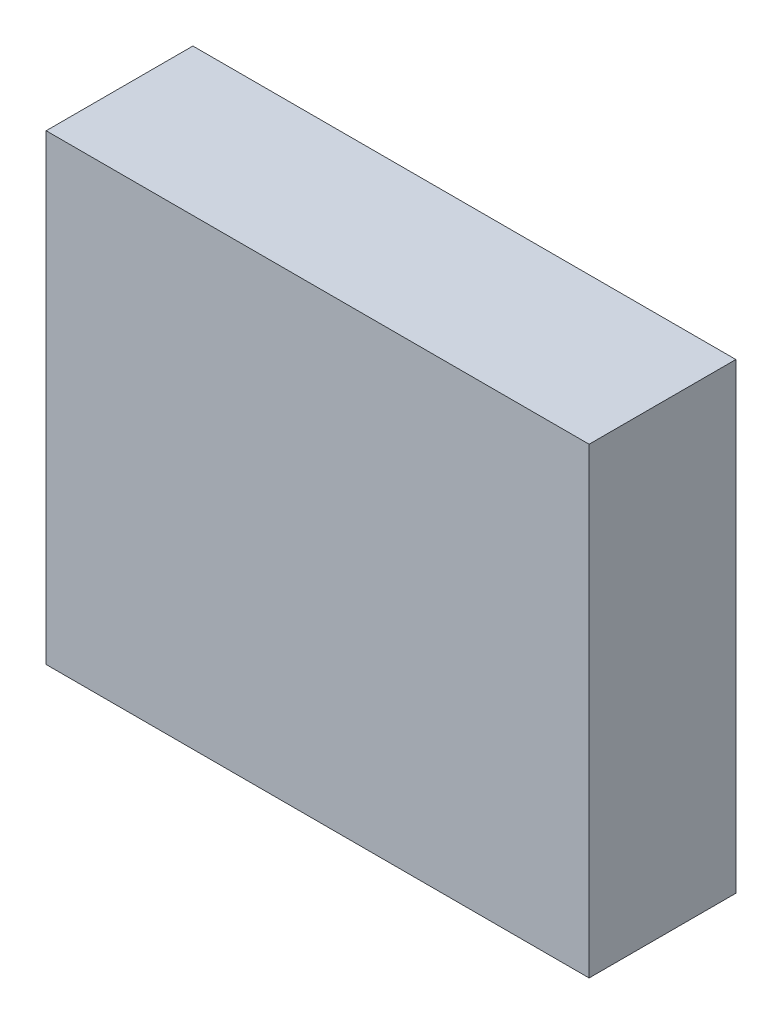
SolidWorks part; units mm, degrees
ref_plane "Front Plane" through (0, 0, 0) normal (0, 0, 1) x (1, 0, 0)
ref_plane "Top Plane" through (0, 0, 0) normal (0, 1, 0) x (1, 0, 0)
ref_plane "Right Plane" through (0, 0, 0) normal (1, 0, 0) x (0, 0, -1)
sketch "Sketch1" plane through (0, 0, 0) normal (0, 0, 1) x (1, 0, 0)
  line L1 (-37, -31.5) -> (37, -31.5)
  line L2 (-37, -31.5) -> (-37, 31.5)
  line L3 (-37, 31.5) -> (37, 31.5)
  line L4 (37, -31.5) -> (37, 31.5)
  line L5 (0, 31.5) -> (0, -31.5) construction
  line L6 (-37, 0) -> (37, 0) construction
  point P0 (0, 0)
  dimension "D1" = 74
  dimension "D2" = 63
extrude "Mold Base" add sketch "Sketch1" along normal blind 20
sketch "Sketch2" plane through (0, 0, 0) normal (0, 0, -1) x (-1, 0, 0)
  line L0 (-37, 31.5) -> (37, 31.5) construction
  line L1 (-32, -26.5) -> (32, -26.5)
  line L2 (-32, -26.5) -> (-32, 26.5)
  line L3 (-32, 26.5) -> (32, 26.5)
  line L4 (32, -26.5) -> (32, 26.5)
  line L5 (0, 26.5) -> (0, -26.5) construction
  line L6 (-32, 0) -> (32, 0) construction
  line L7 (-37, -31.5) -> (-37, 31.5) construction
  point P0 (0, 0)
  dimension "D1" = 5
  dimension "D2" = 5
extrude "Mold Cut" cut sketch "Sketch2" against normal blind 10
sketch "Sketch3" plane through (0, 0, 10) normal (0, 0, -1) x (-1, 0, 0)
  line L0 (0, 2.5) -> (0, -2.5) construction
  line L1 (0, 2.5) -> (0, -2.5)
  arc A0 (0, -2.5) -> (0, 2.5) centre (0, 0) ccw
  dimension "D1" = 5
revolve "Mold" cut sketch "Sketch3" angle 360 about L0 other way angle 360
pattern_linear "LPattern1" count 3 spacing 10 along (0, 1, 0) count 3 spacing 10 along (-1, 0, 0) of "Mold"
pattern_linear "LPattern2" count 3 spacing 10 along (1, 0, 0) count 3 spacing 10 along (0, -1, 0) of "LPattern1"
